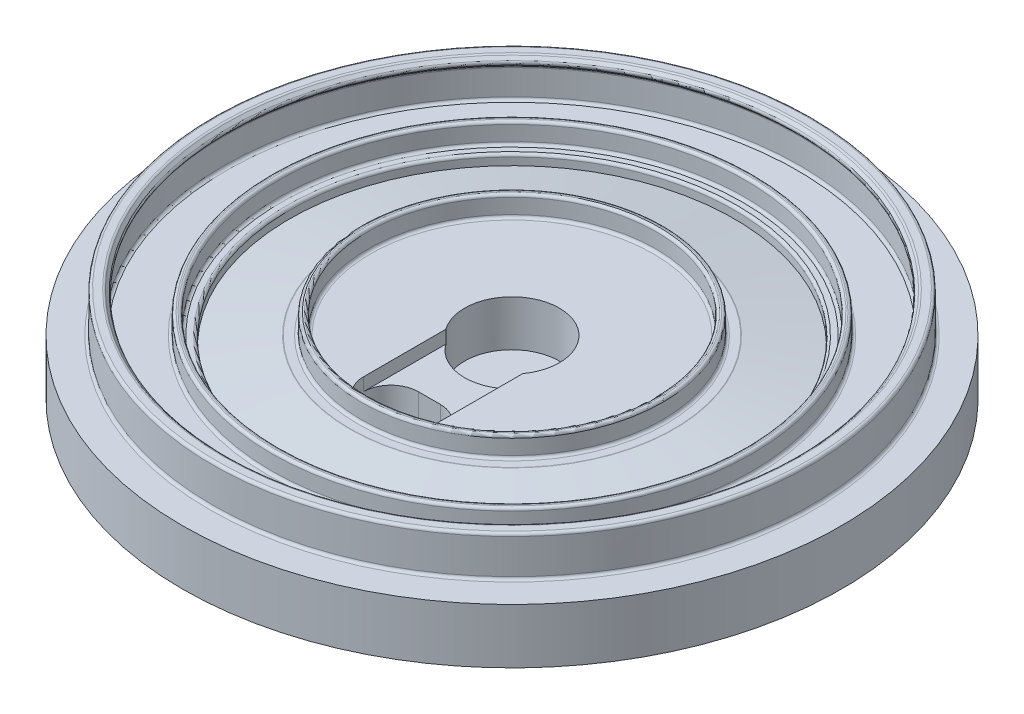
SolidWorks part; units mm, degrees
ref_plane "Front Plane" through (0, 0, 0) normal (0, 0, 1) x (1, 0, 0)
ref_plane "Top Plane" through (0, 0, 0) normal (0, 1, 0) x (1, 0, 0)
ref_plane "Right Plane" through (0, 0, 0) normal (1, 0, 0) x (0, 0, -1)
sketch "Sketch1" plane through (0, 0, 0) normal (0, 1, 0) x (1, 0, 0)
  circle A0 centre (0, 0) radius 60
  circle A1 centre (0, 0) radius 40
  circle A2 centre (0, 0) radius 30
  dimension "D1" = 60
  dimension "D2" = 80
  dimension "D3" = 120
extrude "Boss-Extrude1" add sketch "Sketch1" along normal blind 10 contours A0
sketch "Sketch2" plane through (0, 0, 0) normal (0, 0, 1) x (1, 0, 0)
  line L0 (0, 10) -> (-29.5, 10)
  line L1 (60, 10) -> (-60, 10) construction
  line L2 (-29.5, 10) -> (-40.5, 8.127)
  line L3 (-40.5, 8.127) -> (-40.5, 10)
  line L4 (-40.5, 10) -> (-29.5, 10)
  line L5 (0, 10) -> (0, 0) construction
  dimension "D1" = 11
  dimension "D2" = 29.5
  dimension "D3" = 1.873
revolve "Cut-Revolve1" cut sketch "Sketch2" angle 360 about L5
sketch "Sketch3" plane through (0, 10, 0) normal (0, 1, 0) x (1, 0, 0)
  circle A0 centre (0, 0) radius 27.5
  circle A1 centre (0, 0) radius 26.25
  circle A2 centre (0, 0) radius 42.5
  circle A3 centre (0, 0) radius 43.75
  dimension "D1" = 55
  dimension "D2" = 52.5
  dimension "D3" = 85
  dimension "D4" = 87.5
extrude "Boss-Extrude2" add sketch "Sketch3" along normal blind 3.723 contours A1 | A0 | A2 | A3
fillet "Fillet1" radius 0.5 10 edges at (0, 10, 26.25) (0, 10, 27.5) (0, 10, 43.75) (0, 10, 42.5) (0, 10, 40.5) (0, 13.723, 27.5) (0, 13.723, 26.25) (0, 13.723, 43.75) (0, 13.723, 42.5) (0, 10, 29.5)
sketch "Sketch5" plane through (0, 0, 0) normal (0, 0, 1) x (1, 0, 0)
  line L0 (0, 10) -> (-52.5, 10) construction
  line L1 (60, 10) -> (-60, 10) construction
  line L2 (-52.5, 10) -> (-54.5, 10)
  line L3 (-54.5, 10) -> (-54.5, 17.323)
  line L4 (-54.5, 17.323) -> (-52.5, 17.323)
  line L5 (-52.5, 17.323) -> (-51.5, 16.323)
  line L6 (-51.5, 16.323) -> (-52.5, 15.323)
  line L7 (-52.5, 15.323) -> (-52.5, 10)
  line L8 (0, 10) -> (0, 24.5479) construction
  line L9 (0, -7.5476) -> (0, 7.5476) construction
  dimension "D1" = 52.5
  dimension "D2" = 7.323
  dimension "D3" = 1
  dimension "D4" = 1
  dimension "D5" = 2
  dimension "D6" = 2
revolve "Revolve1" add sketch "Sketch5" angle 360 about L8
fillet "Fillet2" radius 0.5 6 edges at (0, 10, -52.5) (0, 15.323, -52.5) (0, 17.323, -52.5) (0, 16.323, -51.5) (0, 10, -54.5) (0, 17.323, -54.5)
sketch "Sketch6" plane through (0, 10, 0) normal (0, 1, 0) x (1, 0, 0)
  circle A0 centre (0, 0) radius 8.625
  dimension "D1" = 17.25
extrude "Cut-Extrude1" cut sketch "Sketch6" against normal blind 8.354
sketch "Sketch9" plane through (0, 10, 0) normal (0, 1, 0) x (1, 0, 0)
  line L1 (-7, -5.0389) -> (7, -5.0389)
  line L2 (-7, -5.0389) -> (-7, -20.0389)
  line L3 (-7, -20.0389) -> (7, -20.0389)
  line L4 (7, -5.0389) -> (7, -20.0389)
  circle A0 centre (0, 0) radius 8.625 construction
  circle A1 centre (0, 0) radius 8.625 construction
  point P6 (0, 0)
  point P7 (0, 0)
  dimension "D1" = 15
  dimension "D2" = 14
extrude "Cut-Extrude2" cut sketch "Sketch9" against normal blind 2.354
sketch "Sketch10" plane through (0, 10, 0) normal (0, 1, 0) x (1, 0, 0)
  line L0 (2, -20.0389) -> (-2, -20.0389) construction
  line L1 (-7, -20.0389) -> (7, -20.0389) construction
  line L2 (2, -25.0389) -> (-2, -25.0389)
  line L3 (2, -15.0389) -> (-2, -15.0389)
  arc A0 (2, -25.0389) -> (2, -15.0389) centre (2, -20.0389) ccw
  arc A1 (-2, -15.0389) -> (-2, -25.0389) centre (-2, -20.0389) ccw
  point P4 (0, -20.0389)
  dimension "D1" = 5
extrude "Cut-Extrude3" cut sketch "Sketch10" against normal blind 10
